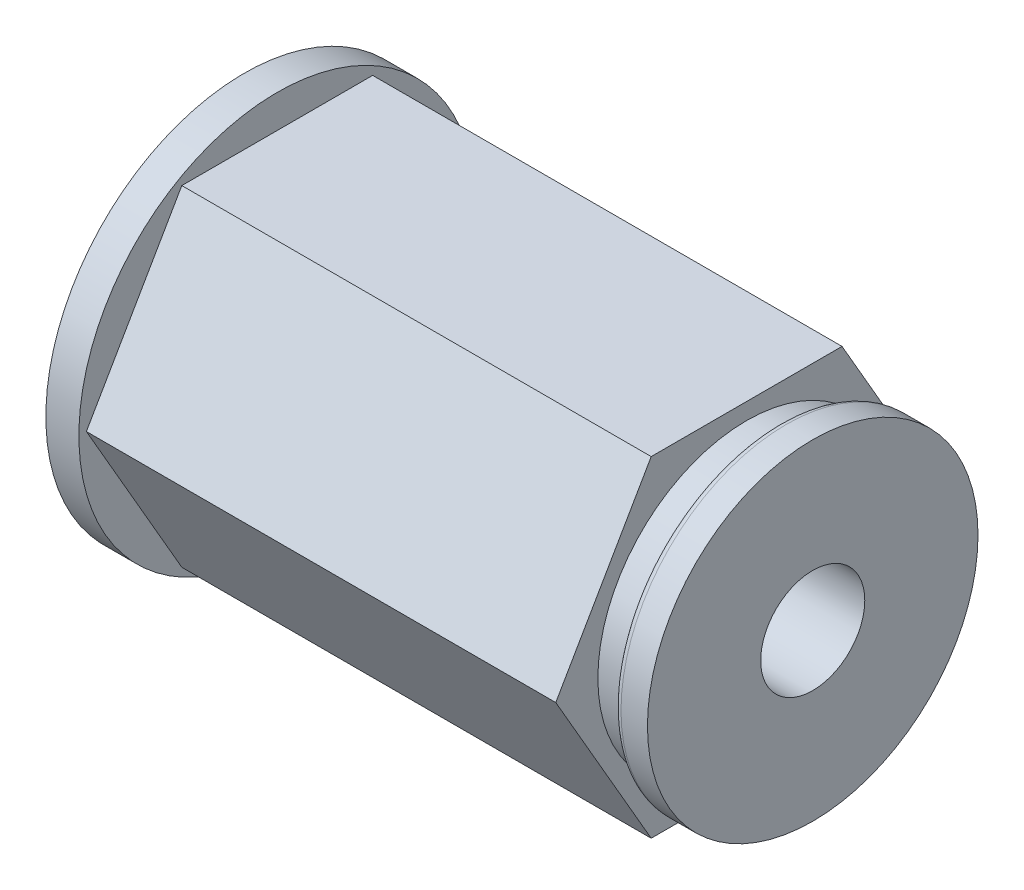
SolidWorks part; units mm, degrees
ref_plane "Front" through (0, 0, 0) normal (0, 0, 1) x (1, 0, 0)
ref_plane "Top" through (0, 0, 0) normal (0, 1, 0) x (1, 0, 0)
ref_plane "Right" through (0, 0, 0) normal (1, 0, 0) x (0, 0, -1)
sketch "Sketch2" plane through (0, 0, 0) normal (1, 0, 0) x (0, 0, -1)
  circle A0 centre (0, 0) radius 7.62
  dimension "D1" = 15.24
extrude "Boss-Extrude1" add sketch "Sketch2" against normal blind 1.27
sketch "Sketch3" plane through (0, 0, 0) normal (1, 0, 0) x (0, 0, -1)
  line L1 (-3.6662, 6.35) -> (-7.3323, 0)
  line L2 (-7.3323, 0) -> (-3.6662, -6.35)
  line L3 (-3.6662, -6.35) -> (3.6662, -6.35)
  line L4 (3.6662, -6.35) -> (7.3323, 0)
  line L5 (7.3323, 0) -> (3.6662, 6.35)
  line L6 (3.6662, 6.35) -> (-3.6662, 6.35)
  circle A0 centre (0, 0) radius 6.35 construction
  dimension "D1" = 12.7
extrude "Boss-Extrude2" add sketch "Sketch3" along normal blind 18.034
sketch "Sketch4" plane through (18.034, 0, 0) normal (1, 0, 0) x (0, 0, -1)
  circle A0 centre (0, 0) radius 5.715
  dimension "D1" = 11.43
extrude "Boss-Extrude3" add sketch "Sketch4" along normal blind 1.27
sketch "Sketch5" plane through (19.304, 0, 0) normal (1, 0, 0) x (0, 0, -1)
  circle A0 centre (0, 0) radius 6.35
  dimension "D1" = 12.7
extrude "Boss-Extrude4" add sketch "Sketch5" along normal blind 1.27
fillet "Fillet1" radius 0.254 2 edges at (19.304, 0, -6.35) (19.304, 0, -5.715)
sketch "Sketch6" plane through (20.574, 0, 0) normal (1, 0, 0) x (0, 0, -1)
  circle A0 centre (0, 0) radius 2
  dimension "D1" = 4
extrude "Cut-Extrude1" cut sketch "Sketch6" against normal up to surface (21.844 mm away) up to face at (-1.27, 0, -7.62)
